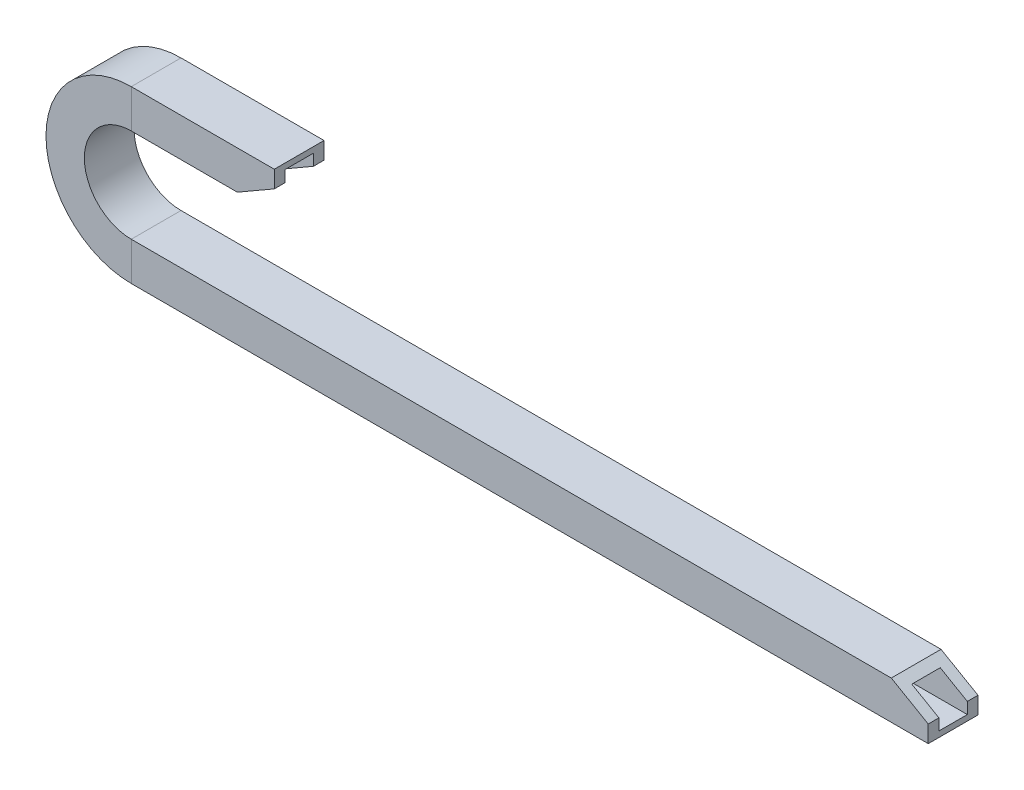
SolidWorks part; units mm, degrees
ref_plane "Front Plane" through (0, 0, 0) normal (0, 0, 1) x (1, 0, 0)
ref_plane "Top Plane" through (0, 0, 0) normal (0, 1, 0) x (1, 0, 0)
ref_plane "Right Plane" through (0, 0, 0) normal (1, 0, 0) x (0, 0, -1)
sketch "Sketch1" plane through (0, 0, 0) normal (0, 0, 1) x (1, 0, 0)
  line L0 (-26.2, 66.98) -> (-54.5034, 66.98)
  line L1 (-26.2, -14.4081) -> (-26.2, 14.4081) construction
  line L2 (203.818, 7) -> (-54.5034, 7)
  line L3 (203.818, -7.1175) -> (203.818, -31.5825) construction
  line L4 (-22, 66.98) -> (22, 66.98) construction
  line L6 (-54.5034, 66.98) -> (-54.5034, 7) construction
  arc A0 (-54.5034, 66.98) -> (-54.5034, 7) centre (-54.5034, 36.99) ccw
ref_plane "Plane1" through (203.818, 7, 0) normal (-1, 0, 0) x (0, 0, 1)
sketch "Sketch2" plane through (203.818, 7, 0) normal (-1, 0, 0) x (0, 0, 1)
  line L0 (8.75, 13.5) -> (8.75, 0)
  line L1 (8.75, 13.5) -> (-8.75, 13.5)
  line L2 (8.75, 0) -> (-8.75, 0)
  line L3 (-8.75, 13.5) -> (-8.75, 0)
  line L4 (8.75, 13.5) -> (-8.75, 0) construction
  line L5 (8.75, 0) -> (-8.75, 13.5) construction
  point P0 (0, 0)
  point P1 (0, 6.75)
  dimension "D1" = 13.5
  dimension "D2" = 17.5
sweep "Sweep1" add profiles "Sketch2" path "Sketch1"
sketch "Sketch3" plane through (0, 0, 8.75) normal (0, 0, 1) x (1, 0, 0)
  line L0 (-26.2, 66.98) -> (-26.2, 53.48)
  line L1 (-26.2, 66.98) -> (-4.2, 66.98)
  line L2 (-4.2, 66.98) -> (-4.2, 60.98)
  line L3 (-4.2, 60.98) -> (-17.2, 53.48)
  line L4 (-17.2, 53.48) -> (-26.2, 53.48)
  line L5 (203.818, 20.5) -> (203.818, 7)
  line L6 (203.818, 7) -> (225.818, 7)
  line L7 (225.818, 7) -> (225.818, 13)
  line L8 (225.818, 13) -> (212.818, 20.5)
  line L9 (212.818, 20.5) -> (203.818, 20.5)
  dimension "D1" = 22
  dimension "D2" = 6
  dimension "D3" = 13
extrude "Boss-Extrude1" add sketch "Sketch3" against normal up to surface (17.5 mm away) up to face at (-40.3517, 60.23, -8.75)
sketch "Sketch4" plane through (225.818, 0, 0) normal (1, 0, 0) x (0, 0, -1)
  line L0 (0, 7) -> (0, 20.5) construction
  line L1 (8.75, 7) -> (-8.75, 7) construction
  line L2 (-8.75, 20.5) -> (8.75, 20.5) construction
  line L3 (-5, 9) -> (5, 9)
  line L4 (-5, 9) -> (-5, 18.5)
  line L5 (5, 9) -> (5, 18.5)
  line L6 (-5, 18.5) -> (5, 18.5)
  line L7 (-5, 9) -> (5, 18.5) construction
  line L8 (5, 9) -> (-5, 18.5) construction
  point P7 (0, 13.75)
  point P9 (0, 13.75)
  dimension "D1" = 9.5
  dimension "D2" = 10
sketch "Sketch5" plane through (0, 0, 0) normal (0, 0, 1) x (1, 0, 0)
  line L0 (-26.2, 66.98) -> (-54.5034, 66.98) construction
  line L1 (203.818, 7) -> (-54.5034, 7) construction
  line L2 (-26.2, 66.98) -> (-54.5034, 66.98)
  line L3 (203.818, 7) -> (-54.5034, 7)
  line L4 (-26.2, 66.98) -> (-4.2, 66.98)
  line L5 (203.818, 7) -> (225.818, 7)
  arc A0 (-54.5034, 66.98) -> (-54.5034, 7) centre (-54.5034, 36.99) ccw construction
  arc A1 (-54.5034, 66.98) -> (-54.5034, 7) centre (-54.5034, 36.99) ccw
sweep "Cut-Sweep2" cut profiles "Sketch4" path "Sketch5"
